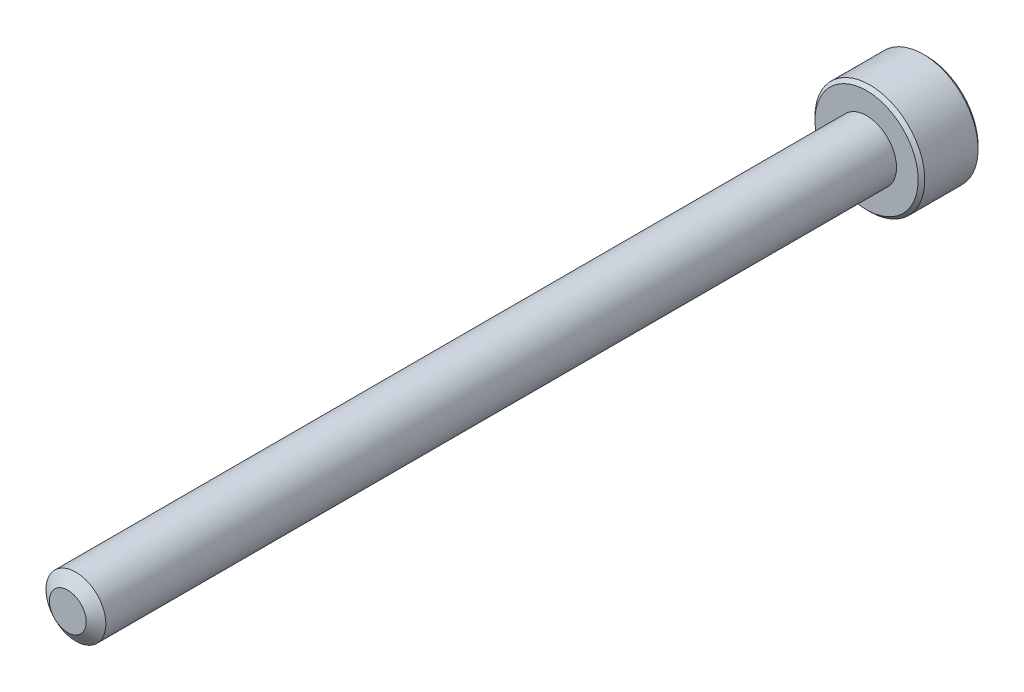
SolidWorks part; units mm, degrees
material "Alloy Steel"
ref_plane "Front Plane" through (0, 0, 0) normal (0, 0, 1) x (1, 0, 0)
ref_plane "Top Plane" through (0, 0, 0) normal (0, 1, 0) x (1, 0, 0)
ref_plane "Right Plane" through (0, 0, 0) normal (1, 0, 0) x (0, 0, -1)
sketch "Sketch1" plane through (0, 0, 0) normal (0, 0, 1) x (1, 0, 0)
  circle A0 centre (0, 0) radius 1.5
  dimension "OD" = 3
extrude "Extrude1" add sketch "Sketch1" against normal blind 40
sketch "Sketch2" plane through (0, 0, 0) normal (0, 0, 1) x (1, 0, 0)
  circle A0 centre (0, 0) radius 1.5 construction
  circle A1 centre (0, 0) radius 1.5
curve "Helix/Spiral1" pitch 0.5 height 40.5 turns 81 parameters "pitch"=0.5
sketch "Sketch3" plane through (0, 0, 0) normal (1, 0, 0) x (0, 0, -1)
  line L0 (-0.4375, 1.5) -> (-0.25, 1.1752)
  line L1 (-0.25, 1.1752) -> (-0.1875, 1.1752)
  line L2 (-0.1875, 1.1752) -> (0, 1.5)
  line L3 (-0.4375, 1.5) -> (0, 1.5)
  line L4 (-0.2187, 1.5) -> (-0.2187, 1.1752) construction
  line L5 (-0.3437, 1.3376) -> (-0.0937, 1.3376) construction
  line L6 (0, 1.5) -> (0, -1.5) construction
  line L7 (0, -1.5) -> (40, -1.5) construction
  point P11 (2.25, -1.5)
  dimension "D1" = 0.0625
  dimension "D2" = 0.25
  dimension "D3" = 60
  dimension "D4" = 2.25
sweep "Cut-Sweep1" [suppressed] cut profiles "Sketch3" path "Helix/Spiral1"
sketch "Sketch4" plane through (0, 0, 0) normal (1, 0, 0) x (0, 0, -1)
  line L0 (0.4053, 1.5) -> (0, 0.9212)
  line L1 (0, 0.9212) -> (0, 1.5)
  line L2 (0.4053, 1.5) -> (0, 1.5)
  line L3 (-0.4375, 1.5) -> (0, 1.5) construction
  line L4 (0, 0) -> (7.0209, 0) construction
  dimension "D1" = 55
  dimension "D2" = 0.254
revolve "Cut-Revolve1" cut sketch "Sketch4" angle 360 about L4
sketch "Sketch5" [suppressed] plane through (0, 0, 0) normal (1, 0, 0) x (0, 0, -1)
  line L0 (40, -1.1822) -> (40, 1.0703) construction
  line L1 (40, 1.5) -> (18.1202, 1.5)
  line L2 (40, 1.5) -> (40, 0)
  line L3 (40, 0) -> (18, 0)
  line L4 (18, 1.1698) -> (18, 0)
  line L5 (18.1202, 1.5) -> (18, 1.1698)
  line L6 (0, 0) -> (9.9695, 0) construction
  point P3 (18, 1.5)
  point P10 (18, 1.5)
  dimension "D1" = 0.3302
  dimension "Thread min" = 18
  dimension "D3" = 20
revolve "partially thread" [suppressed] add sketch "Sketch5" angle 360 about L6
sketch "Sketch6" plane through (0, 0, -40) normal (0, 0, -1) x (-1, 0, 0)
  circle A0 centre (0, 0) radius 2.75
  dimension "head dia" = 5.5
extrude "Extrude2" add sketch "Sketch6" along normal blind 3
sketch "Sketch7" plane through (0, 0, -43) normal (0, 0, -1) x (-1, 0, 0)
  line L1 (0, 1.4434) -> (-1.25, 0.7217)
  line L2 (-1.25, 0.7217) -> (-1.25, -0.7217)
  line L3 (-1.25, -0.7217) -> (0, -1.4434)
  line L4 (0, -1.4434) -> (1.25, -0.7217)
  line L5 (1.25, -0.7217) -> (1.25, 0.7217)
  line L6 (1.25, 0.7217) -> (0, 1.4434)
  circle A0 centre (0, 0) radius 1.25 construction
  dimension "hex dia" = 2.5
extrude "Cut-Extrude1" cut sketch "Sketch7" against normal blind 1.875
sketch "Sketch8" plane through (0, 0, -43) normal (0, 0, -1) x (-1, 0, 0)
  circle A0 centre (0, 0) radius 1.4434
extrude "Cut-Extrude2" cut sketch "Sketch8" against normal through all draft 45
chamfer "Chamfer1" distance 0.165 angle 45 2 edges at (-2.75, 0, -43) (-2.75, 0, -40)
sketch "Sketch9" plane through (0, 0, 0) normal (1, 0, 0) x (0, 0, -1)
  line L0 (0, 1.5) -> (0, -1.5) construction
  line L1 (2.75, 1.5) -> (2.75, -1.5) construction
  dimension "D1" = 2.75
sketch "Sketch10" plane through (0, 0, 0) normal (1, 0, 0) x (0, 0, -1)
  line L0 (40, 1.5) -> (40, 0)
  line L1 (40, 1.5) -> (39.875, 1.5)
  line L2 (39.875, 1.5) -> (39.2537, 0)
  line L3 (40, 0) -> (39.2537, 0)
  line L4 (40, 2.585) -> (40, -2.585) construction
  dimension "D1" = 22.5
  dimension "D2" = 0.125
revolve "Revolve1" add sketch "Sketch10" angle 360 about L3
equation "\"D3@Helix/Spiral1\" = \"screw length@Extrude1\"+\"pitch@Helix/Spiral1\""
equation "\"D1@Sketch3\" = \"pitch@Helix/Spiral1\"*.125"
equation "\"D2@Sketch3\" = \"pitch@Helix/Spiral1\"*.5"
equation "\"D1@Cut-Extrude1\" = \"hex dia@Sketch7\"*.75"
equation "\"D1@Chamfer1\" = \"head dia@Sketch6\"*.03"
equation "\"D1@Sketch9\" = \"pitch@Helix/Spiral1\"*5.5"
equation "\"D2@Sketch10\" = \"pitch@Helix/Spiral1\"*.25"
equation "\"D4@Sketch3\" = \"pitch@Helix/Spiral1\"*4.50"
